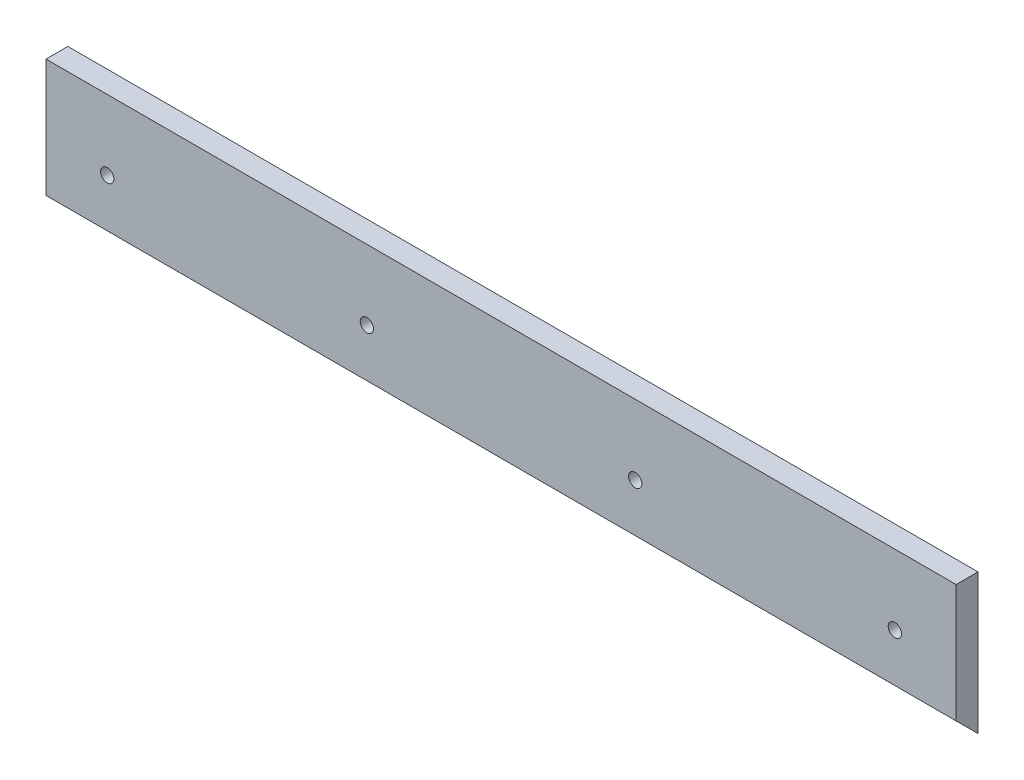
SolidWorks part; units mm, degrees
ref_plane "Front Plane" through (0, 0, 0) normal (0, 0, 1) x (1, 0, 0)
ref_plane "Top Plane" through (0, 0, 0) normal (0, 1, 0) x (1, 0, 0)
ref_plane "Right Plane" through (0, 0, 0) normal (1, 0, 0) x (0, 0, -1)
sketch "Sketch1" plane through (0, 0, 0) normal (0, 0, 1) x (1, 0, 0)
  line L1 (330.2, 50.8) -> (-330.2, 50.8)
  line L2 (330.2, 50.8) -> (330.2, -50.8)
  line L3 (330.2, -50.8) -> (-330.2, -50.8)
  line L4 (-330.2, 50.8) -> (-330.2, -50.8)
  line L5 (330.2, 50.8) -> (-330.2, -50.8) construction
  line L6 (330.2, -50.8) -> (-330.2, 50.8) construction
  point P0 (0, 0)
  dimension "D1" = 101.6
  dimension "D2" = 660.4
extrude "Boss-Extrude1" add sketch "Sketch1" along normal mid plane 15.875
sketch "Sketch2" plane through (330.2, 0, 0) normal (1, 0, 0) x (0, 0, -1)
  line L0 (-7.9375, 50.8) -> (7.9375, 34.925)
  line L1 (7.9375, -50.8) -> (7.9375, 50.8) construction
  line L2 (7.9375, 34.925) -> (7.9375, 50.8)
  line L3 (7.9375, 50.8) -> (-7.9375, 50.8)
  dimension "D1" = 45
extrude "Cut-Extrude1" [suppressed] cut sketch "Sketch2" against normal through all both and the other way through all
sketch "Sketch3" plane through (330.2, 0, 0) normal (1, 0, 0) x (0, 0, -1)
  line L0 (7.9375, -50.8) -> (-7.9375, -34.925)
  line L1 (-7.9375, -50.8) -> (-7.9375, 50.8) construction
  line L2 (-7.9375, -34.925) -> (-7.9375, -50.8)
  line L3 (-7.9375, -50.8) -> (7.9375, -50.8)
  dimension "D1" = 45
extrude "Cut-Extrude2" cut sketch "Sketch3" against normal through all both and the other way through all
sketch "Sketch4" plane through (0, 0, -7.9375) normal (0, 0, -1) x (-1, 0, 0)
  line L0 (0, 0) -> (0, 50.8) construction
  line L1 (-330.2, 50.8) -> (330.2, 50.8) construction
  line L2 (-330.2, -50.8) -> (-330.2, 50.8) construction
  circle A0 centre (-285.75, 0) radius 13.1826
  circle A1 centre (-285.75, 0) radius 4.826
  circle A2 centre (-97.3667, 0) radius 13.1826
  circle A3 centre (-97.3667, 0) radius 4.826
  circle A4 centre (97.3667, 0) radius 4.826
  circle A5 centre (285.75, 0) radius 4.826
  circle A6 centre (285.75, 0) radius 13.1826
  circle A7 centre (97.3667, 0) radius 13.1826
  dimension "D1" = 9.652
  dimension "D2" = 26.3652
  dimension "D4" = 194.7333
  dimension "D3" = 44.45
extrude "Cut-Extrude3" cut sketch "Sketch4" against normal through all both and the other way through all contours A1 | A3 | A4 | A5 region at (285.75, 0, -7.9375) region at (97.3667, 0, -7.9375) region at (-97.3667, 0, -7.9375) region at (-285.75, 0, -7.9375)
extrude "Cut-Extrude4" cut sketch "Sketch4<3>" against normal blind 8.128
sketch "Sketch4<3>" plane through (0, 0, -7.9375) normal (0, 0, -1) x (-1, 0, 0) same geometry as "Sketch4"
